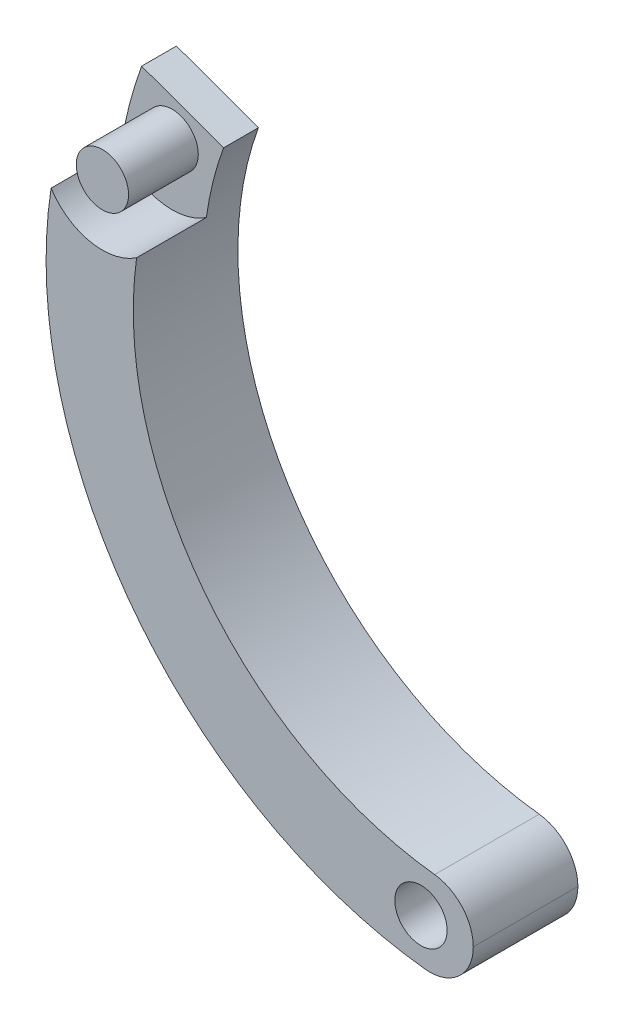
SolidWorks part; units mm, degrees
ref_plane "Plan de face" through (0, 0, 0) normal (0, 0, 1) x (1, 0, 0)
ref_plane "Plan de dessus" through (0, 0, 0) normal (0, 1, 0) x (1, 0, 0)
ref_plane "Plan de droite" through (0, 0, 0) normal (1, 0, 0) x (0, 0, -1)
sketch "Esquisse2" plane through (0, 0, 0) normal (0, 0, 1) x (1, 0, 0)
  line L0 (0, 0) -> (0, 39) construction
  line L1 (0, 39) -> (-36.648, 52.3388) construction
  line L2 (0, 0) -> (0, -10)
  line L3 (-36.648, 52.3388) -> (-46.0449, 55.759)
  arc A0 (0, 0) -> (-36.648, 52.3388) centre (0, 39) cw
  arc A1 (0, -10) -> (-46.0449, 55.759) centre (0, 39) cw
  point P7 (0, 0)
  dimension "D1" = 39
  dimension "D3" = 10
  dimension "D2" = 110
extrude "Boss.-Extru.1" add sketch "Esquisse2" along normal blind 12
sketch "Esquisse3" plane through (0, 0, 12) normal (0, 0, 1) x (1, 0, 0)
  line L0 (0, -10) -> (0, 0) construction
  line L2 (-6, -4.589) -> (0, 39) construction
  line L3 (-36.648, 52.3388) -> (-46.0449, 55.759) construction
  circle A0 centre (-6, -4.589) radius 3
  arc A1 (0, -5) -> (-41.3465, 54.0489) centre (0, 39) cw construction
  point P5 (0, 0)
  point P6 (-6.3093, -4.5453)
  dimension "D2" = 6
  dimension "D1" = 6
extrude "Enlèv. mat.-Extru.1" cut sketch "Esquisse3" against normal through all both and the other way through all
fillet "Congé1" radius 5 2 edges at (0, -10, 6) (0, 0, 6)
sketch "Esquisse5" plane through (0, 0, 12) normal (0, 0, 1) x (1, 0, 0)
  line L0 (-36.648, 52.3388) -> (-46.0449, 55.759) construction
  arc A0 (-41.3465, 54.0489) -> (-6, -4.589) centre (0, 39) ccw construction
  arc A1 (-36.648, 52.3388) -> (-4.4318, 0.2526) centre (0, 39) ccw construction
  circle A2 centre (-42.5423, 50.2318) radius 3
  circle A3 centre (-42.5423, 50.2318) radius 7
  dimension "D1" = 6
  dimension "D2" = 14
  dimension "D3" = 4
extrude "Enlèv. mat.-Extru.2" cut sketch "Esquisse5" against normal blind 8
